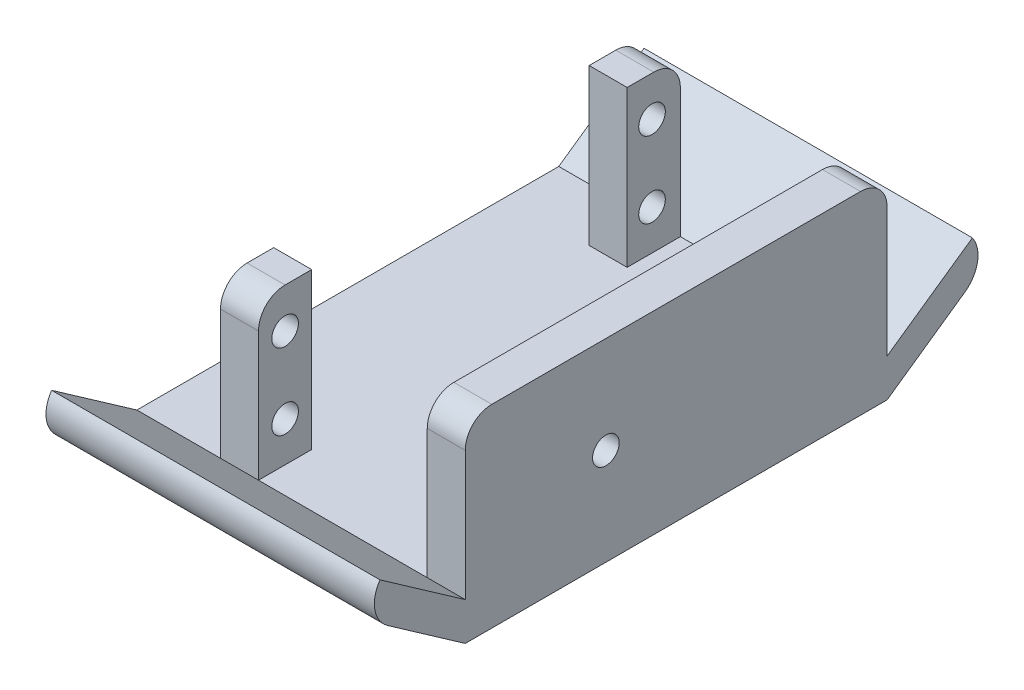
SolidWorks part; units mm, degrees
ref_plane "Front Plane" through (0, 0, 0) normal (0, 0, 1) x (1, 0, 0)
ref_plane "Top Plane" through (0, 0, 0) normal (0, 1, 0) x (1, 0, 0)
ref_plane "Right Plane" through (0, 0, 0) normal (1, 0, 0) x (0, 0, -1)
sketch "Sketch of Servo Motor" plane through (0, 0, 0) normal (0, 1, 0) x (1, 0, 0)
  line L0 (0, 0) -> (27.2, 0) construction
  line L1 (27.2, 0) -> (27.2, -41.5) construction
  line L2 (27.2, -41.5) -> (0, -41.5) construction
  line L3 (0, -41.5) -> (0, -48.5) construction
  line L4 (0, -48.5) -> (-2.8, -48.5) construction
  line L5 (-2.8, -48.5) -> (-2.8, -41.5) construction
  line L6 (-2.8, -41.5) -> (-11, -41.5) construction
  line L7 (-11, -41.5) -> (-11, 0) construction
  line L8 (-11, 0) -> (-2.8, 0) construction
  line L9 (-2.8, 0) -> (-2.8, 7) construction
  line L10 (-2.8, 7) -> (0, 7) construction
  line L11 (0, 7) -> (0, 0) construction
  line L13 (32.2, -48.5) -> (-11, -48.5)
  line L14 (32.2, -48.5) -> (32.2, 7)
  line L15 (32.2, 7) -> (-11, 7)
  line L16 (-11, -48.5) -> (-11, 7)
  dimension "D1" = 38.2
  dimension "D2" = 27.2
  dimension "D3" = 55.5
  dimension "D4" = 41.5
  dimension "D5" = 2.8
  dimension "D6" = 5
extrude "Extrude Base of Foot" add sketch "Sketch of Servo Motor" against normal blind 5
sketch "Positions of Foot Sides" plane through (0, 0, 0) normal (0, 1, 0) x (1, 0, 0)
  line L0 (-11, 0) -> (-2.8, 0) construction
  line L1 (-11, 7) -> (-11, -48.5) construction
  line L2 (-2.8, 0) -> (-2.8, 7) construction
  line L3 (32.2, 7) -> (-11, 7) construction
  line L4 (-2.8, 7) -> (0, 7) construction
  line L5 (0, 7) -> (0, 0) construction
  line L7 (27.2, 0) -> (27.2, -41.5) construction
  line L8 (27.2, -41.5) -> (0, -41.5) construction
  line L9 (0, -41.5) -> (0, -48.5) construction
  line L10 (-11, -48.5) -> (32.2, -48.5) construction
  line L11 (0, -48.5) -> (-2.8, -48.5) construction
  line L12 (-2.8, -48.5) -> (-2.8, -41.5) construction
  line L13 (-2.8, -41.5) -> (-11, -41.5) construction
  line L14 (-11, -41.5) -> (-11, 0) construction
  line L15 (32.2, -48.5) -> (32.2, 7) construction
  line L16 (27.2, -20.75) -> (-11, -20.75) construction
  line L17 (32.2, 7) -> (27.2, 7)
  line L18 (32.2, 7) -> (32.2, -48.5)
  line L19 (32.2, -48.5) -> (27.2, -48.5)
  line L20 (27.2, 7) -> (27.2, -48.5)
  line L21 (0, 0) -> (5, 0)
  line L22 (0, 0) -> (0, 7)
  line L23 (0, 7) -> (5, 7)
  line L24 (5, 0) -> (5, 7)
  line L25 (0, -41.5) -> (5, -41.5)
  line L26 (0, -41.5) -> (0, -48.5)
  line L27 (0, -48.5) -> (5, -48.5)
  line L28 (5, -41.5) -> (5, -48.5)
  dimension "D1" = 2.8
  dimension "D2" = 5
  dimension "D3" = 5
  dimension "D4" = 22.2
  dimension "D5" = 7
extrude "Extrude Sides of Foot" add sketch "Positions of Foot Sides" along normal blind 20.5
fillet "Fillet Top Edges of Sides of Foot" radius 3.5 4 edges at (29.7, 20.5, -7) (2.5, 20.5, -7) (2.5, 20.5, 48.5) (29.7, 20.5, 48.5)
ref_plane "Inside RT Foot Plane" through (-11, 0, 0) normal (-1, 0, 0) x (0, 0, 1)
sketch "Front and Back Foot Lips" plane through (-11, 0, 0) normal (-1, 0, 0) x (0, 0, 1)
  line L0 (20.75, -5) -> (20.75, 20.5) construction
  line L1 (-7, -5) -> (48.5, -5) construction
  line L2 (-3.5, 20.5) -> (45, 20.5) construction
  line L3 (48.5, -5) -> (62.0674, 4.5) construction
  line L6 (48.5, -5) -> (48.5, 17) construction
  line L7 (62.0674, 4.5) -> (59.7182, 7.8551)
  line L8 (59.7182, 7.8551) -> (48.5, 0)
  line L9 (-7, 0) -> (48.5, 0) construction
  line L10 (48.5, 0) -> (48.5, -5)
  line L11 (48.5, -5) -> (62.0674, 4.5)
  line L12 (-7, 0) -> (-7, -5)
  line L13 (-18.2182, 7.8551) -> (-7, 0)
  line L14 (-20.5674, 4.5) -> (-18.2182, 7.8551)
  line L15 (-7, -5) -> (-20.5674, 4.5)
  dimension "D1" = 55
  dimension "D2" = 9.5
  dimension "D3" = 90
  dimension "D4" = 270
extrude "Extrude Foot Lips" add sketch "Front and Back Foot Lips" against normal through all
fillet "Fillet Foot Lips" radius 4.1 2 edges at (10.6, 4.5, 62.0674) (10.6, 4.5, -20.5674)
ref_plane "Top Servo Motor Screw Holes Plane" through (0, 0, 0) normal (-1, 0, 0) x (0, 0, 1)
sketch "Hole Dimensions for M4 Bolt" plane through (0, 0, 0) normal (-1, 0, 0) x (0, 0, 1)
  line L0 (-7, 0) -> (48.5, 0) construction
  line L1 (0, 20.5) -> (0, 0) construction
  line L6 (45, 0) -> (45, 20.5) construction
  line L7 (41.5, 0) -> (48.5, 0) construction
  circle A0 centre (-3.2705, 15.25) radius 1.75
  circle A1 centre (-3.2705, 5.25) radius 1.75
  circle A2 centre (45, 15.25) radius 1.75
  circle A3 centre (45, 5.25) radius 1.75
  dimension "D2" = 3.5
  dimension "D3" = 10
  dimension "D1" = 5.25
  dimension "D4" = 3.2705
extrude "Extrude Cut Hole for M4 Bolt" cut sketch "Hole Dimensions for M4 Bolt" against normal blind 5
ref_plane "Outside Foot Plane" through (32.2, 0, 0) normal (1, 0, 0) x (0, 0, -1)
sketch "Dimensions for Outside Foot M4 Hole" plane through (32.2, 0, 0) normal (1, 0, 0) x (0, 0, -1)
  line L0 (-20.75, -5) -> (-20.75, 20.5) construction
  line L1 (-48.5, -5) -> (7, -5) construction
  line L2 (-45, 20.5) -> (3.5, 20.5) construction
  line L3 (-20.75, 7.75) -> (-48.5, 7.75) construction
  line L4 (-48.5, 0) -> (-48.5, 17) construction
  circle A0 centre (-30, 7.75) radius 1.75
  dimension "D1" = 18.5
  dimension "D2" = 3.5
extrude "Cut-Extrude1" cut sketch "Dimensions for Outside Foot M4 Hole" against normal up to next
